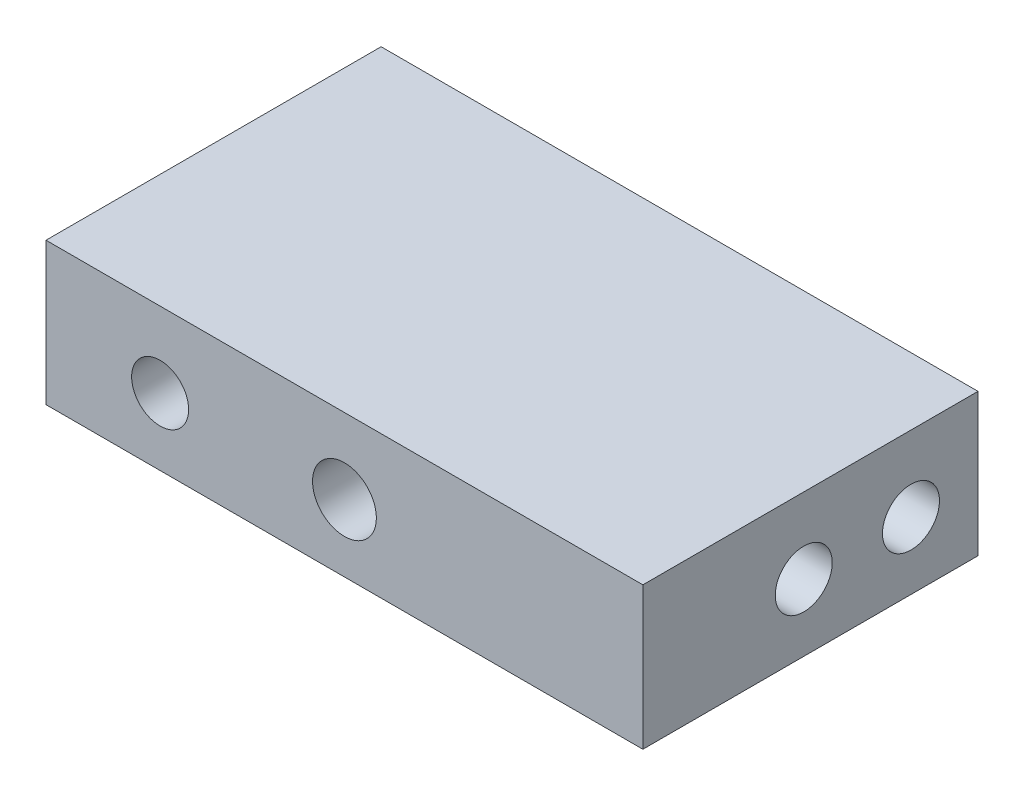
SolidWorks part; units mm, degrees
material "ABS"
ref_plane "X-Y Datum" through (0, 0, 0) normal (0, 0, 1) x (1, 0, 0)
ref_plane "X-Z Datum" through (0, 0, 0) normal (0, 1, 0) x (1, 0, 0)
ref_plane "Y-Z Datum" through (0, 0, 0) normal (1, 0, 0) x (0, 0, -1)
sketch "Sketch1" plane through (0, 0, 0) normal (0, 0, 1) x (1, 0, 0)
  line L1 (-28.275, 6.35) -> (28.275, 6.35)
  line L2 (-28.275, 6.35) -> (-28.275, -6.35)
  line L3 (-28.275, -6.35) -> (28.275, -6.35)
  line L4 (28.275, 6.35) -> (28.275, -6.35)
  line L5 (-28.275, 6.35) -> (28.275, -6.35) construction
  line L6 (-28.275, -6.35) -> (28.275, 6.35) construction
  point P0 (0, 0)
  dimension "D1" = 56.55
  dimension "D2" = 12.7
extrude "Boss-Extrude1" add sketch "Sketch1" along normal blind 31.75 contours L2 L3 L4 L1
sketch "Sketch2" plane through (0, 0, 31.75) normal (0, 0, 1) x (1, 0, 0)
  line L0 (-28.275, 0) -> (28.275, 0) construction
  line L1 (-28.275, 6.35) -> (-28.275, -6.35) construction
  line L2 (28.275, 6.35) -> (28.275, -6.35) construction
  line L3 (-17.4625, 0) -> (17.4625, 0) construction
  circle A0 centre (17.4625, 0) radius 2.7 construction
  circle A1 centre (-17.4625, 0) radius 2.7
  circle A2 centre (0, 0) radius 3.025
  point P10 (0, 0)
  dimension "D1" = 5.4
  dimension "D3" = 6.05
  dimension "D2" = 34.925
extrude "Cut-Extrude1" cut sketch "Sketch2" against normal blind 10 contours A1 L0 L3 | L0 A1 L3 | L0 L3 A0 | L3 L0 A0 | A2 region at (-17.4625, 0, 31.75) region at (0, 0, 31.75)
sketch "Sketch3" plane through (-28.275, 0, 0) normal (-1, 0, 0) x (0, 0, 1)
  line L0 (31.75, 0) -> (0, 0) construction
  line L1 (31.75, 6.35) -> (31.75, -6.35) construction
  line L2 (0, 6.35) -> (0, -6.35) construction
  circle A0 centre (6.35, 0) radius 2.7
  circle A1 centre (16.51, 0) radius 2.7
  dimension "D1" = 5.4
  dimension "D2" = 10.16
  dimension "D3" = 6.35
extrude "Cut-Extrude2" cut sketch "Sketch3" against normal blind 8 contours A0 L0 | L0 A0 | A1 L0 | L0 A1 region at (-28.275, -1.1459, 16.51) region at (-28.275, 1.1459, 16.51) region at (-28.275, -1.1459, 6.35) region at (-28.275, 1.1459, 6.35)
sketch "Sketch4" plane through (0, 6.35, 0) normal (0, 1, 0) x (1, 0, 0)
  line L4 (28.275, 0) -> (-28.275, 0)
  line L5 (-28.275, 0) -> (-28.275, -31.75)
  line L6 (-28.275, -31.75) -> (28.275, -31.75)
  line L7 (28.275, -31.75) -> (28.275, 0)
  line L8 (28.275, 0) -> (-28.275, 0)
  line L9 (-28.275, 0) -> (-28.275, -31.75)
  line L10 (-28.275, -31.75) -> (28.275, -31.75)
  line L11 (28.275, -31.75) -> (28.275, 0)
  dimension "D1" = 0
extrude "Boss-Extrude2" add sketch "Sketch4" along normal blind 0.7937
mirror "Mirror1" about plane through (0, 0, 0) normal (1, 0, 0) of "Cut-Extrude2"
